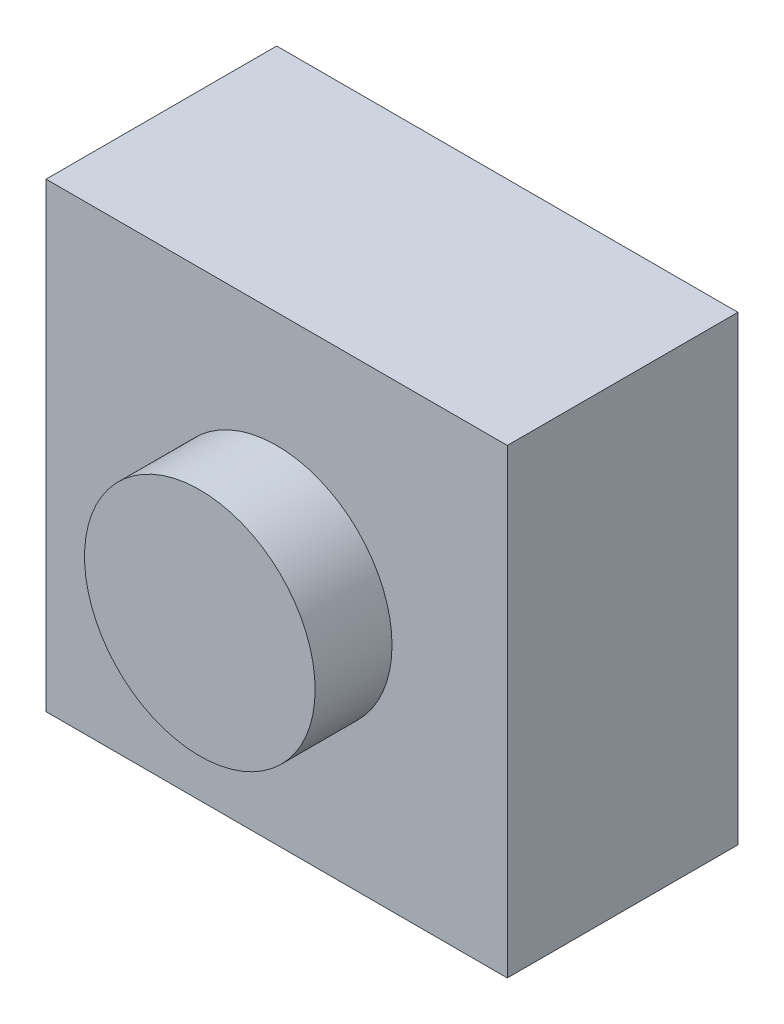
SolidWorks part; units mm, degrees
ref_plane "Спереди" through (0, 0, 0) normal (0, 0, 1) x (1, 0, 0)
ref_plane "Сверху" through (0, 0, 0) normal (0, 1, 0) x (1, 0, 0)
ref_plane "Справа" through (0, 0, 0) normal (1, 0, 0) x (0, 0, -1)
sketch "Эскиз1" plane through (0, 0, 0) normal (0, 0, 1) x (1, 0, 0)
  line L0 (-6, 6) -> (0, 0) construction
  line L1 (0, 0) -> (-6, 0)
  line L2 (0, 0) -> (0, 6)
  line L3 (0, 6) -> (-6, 6)
  line L4 (-6, 0) -> (-6, 6)
  line L5 (0, 6) -> (-6, 0) construction
  circle A0 centre (-3, 3) radius 1.5
  dimension "D3" = 3
  dimension "D1" = 6
  dimension "D2" = 6
extrude "Бобышка-Вытянуть1" add sketch "Эскиз1" along normal blind 3 contours L4 L1 L2 L3 A0 | A0 | A0 | L2 L1 L4 L3 region at (-3, 0.0849, 0) region at (-3, 3, 0)
extrude "Бобышка-Вытянуть2" add sketch "Эскиз1<3>" along normal blind 4 contours A0 region at (-3, 3, 0)
sketch "Эскиз1<3>" plane through (0, 0, 0) normal (0, 0, 1) x (1, 0, 0) same geometry as "Эскиз1"
